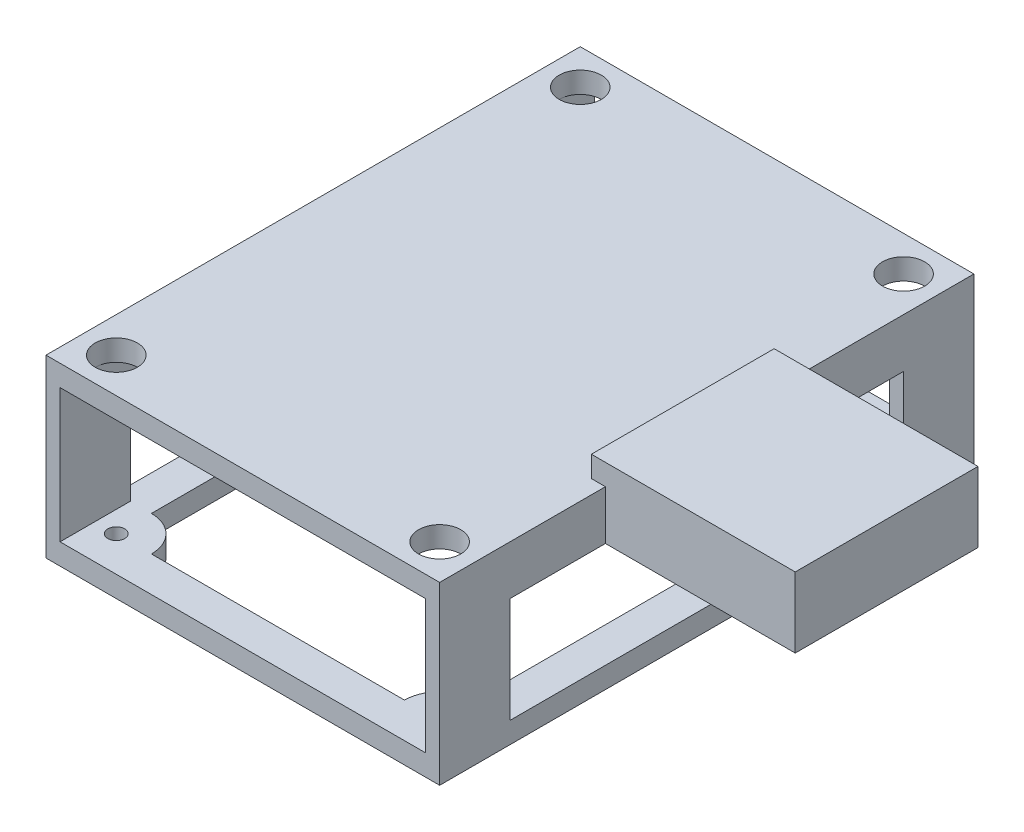
SolidWorks part; units mm, degrees
ref_plane "Front Plane" through (0, 0, 0) normal (0, 0, 1) x (1, 0, 0)
ref_plane "Top Plane" through (0, 0, 0) normal (0, 1, 0) x (1, 0, 0)
ref_plane "Right Plane" through (0, 0, 0) normal (1, 0, 0) x (0, 0, -1)
sketch "Sketch1" plane through (0, 0, 0) normal (0, 1, 0) x (1, 0, 0)
  line L0 (51, 71) -> (51, 5) construction
  line L1 (0, 0) -> (56, 0)
  line L2 (0, 0) -> (0, 76)
  line L3 (0, 76) -> (56, 76)
  line L4 (56, 0) -> (56, 76)
  line L5 (5, 5) -> (51, 5) construction
  circle A0 centre (5, 71) radius 1.2
  circle A1 centre (51, 71) radius 1.2
  circle A2 centre (5, 5) radius 1.2
  circle A3 centre (51, 5) radius 1.2
  point P13 (51, 38)
  point P14 (56, 38)
  point P15 (28, 5)
  point P16 (28, 0)
  dimension "D3" = 2.4
  dimension "D6" = 2.4
  dimension "D7" = 2.4
  dimension "D8" = 2.4
  dimension "D1" = 56
  dimension "D2" = 76
  dimension "D4" = 46
  dimension "D5" = 66
extrude "Boss-Extrude1" add sketch "Sketch1" along normal blind 25
sketch "Sketch2" plane through (0, 0, -76) normal (0, 0, -1) x (-1, 0, 0)
  line L0 (-56, 25) -> (0, 25) construction
  line L1 (-54, 22) -> (-2, 22)
  line L2 (-54, 22) -> (-54, 3)
  line L3 (-54, 3) -> (-2, 3)
  line L4 (-2, 22) -> (-2, 3)
  line L6 (-56, 0) -> (0, 0) construction
  line L7 (-56, 25) -> (-56, 0) construction
  line L8 (0, 25) -> (0, 0) construction
  dimension "D1" = 3
  dimension "D2" = 3
  dimension "D3" = 2
  dimension "D4" = 2
extrude "Cut-Extrude1" cut sketch "Sketch2" against normal through all
sketch "Sketch3" plane through (0, 0, 0) normal (0, -1, 0) x (1, 0, 0)
  line L1 (10, -5) -> (46, -5)
  line L2 (5, -10) -> (5, -66)
  line L3 (10, -71) -> (46, -71)
  line L4 (51, -10) -> (51, -66)
  arc A0 (5, -10) -> (10, -5) centre (5, -5) ccw
  arc A1 (46, -5) -> (51, -10) centre (51, -5) ccw
  arc A2 (51, -66) -> (46, -71) centre (51, -71) ccw
  arc A3 (10, -71) -> (5, -66) centre (5, -71) ccw
extrude "Cut-Extrude2" cut sketch "Sketch3" against normal up to next
sketch "Sketch4" plane through (54, 0, 0) normal (-1, 0, 0) x (0, 0, 1)
  line L0 (0, 3) -> (-76, 3) construction
  line L1 (-66, 3) -> (-10, 3)
  line L2 (-66, 3) -> (-66, 18)
  line L3 (-66, 18) -> (-10, 18)
  line L4 (-10, 3) -> (-10, 18)
  line L5 (-10, 3) -> (-66, 3) construction
  line L6 (-76, 22) -> (-76, 3) construction
  line L7 (0, 22) -> (0, 3) construction
  dimension "D1" = 10
  dimension "D2" = 10
  dimension "D3" = 15
extrude "Cut-Extrude3" cut sketch "Sketch4" against normal through all both and the other way through all
sketch "Sketch7" plane through (0, 25, 0) normal (0, 1, 0) x (1, 0, 0)
  line L0 (28, 76) -> (28, 0) construction
  line L1 (56, 76) -> (0, 76) construction
  line L2 (0, 0) -> (56, 0) construction
  circle A0 centre (5, 71) radius 3
  circle A1 centre (5, 5) radius 3
  circle A2 centre (51, 5) radius 3
  circle A3 centre (51, 71) radius 3
  dimension "D2" = 6
extrude "Cut-Extrude4" cut sketch "Sketch7" against normal up to next and the other way through all
sketch "Sketch8" plane through (56, 0, 0) normal (1, 0, 0) x (0, 0, -1)
  line L0 (10, 18) -> (66, 18) construction
  line L1 (23.5828, 18) -> (49.5828, 18)
  line L2 (23.5828, 18) -> (23.5828, 28)
  line L3 (23.5828, 28) -> (49.5828, 28)
  line L4 (49.5828, 18) -> (49.5828, 28)
  dimension "D1" = 26
  dimension "D2" = 10
sketch "Sketch9" plane through (0, 18, 0) normal (0, -1, 0) x (1, 0, 0)
  line L0 (56, -23.5828) -> (56, -49.5828) construction
  line L1 (56, -23.5828) -> (54, -23.5828)
  line L2 (56, -23.5828) -> (56, -49.5828)
  line L3 (56, -49.5828) -> (54, -49.5828)
  line L4 (54, -23.5828) -> (54, -49.5828)
  line L5 (54, -5) -> (54, -71) construction
extrude "Cut-Extrude7" cut sketch "Sketch9" against normal up to next
sketch "Sketch12" plane through (54, 0, 0) normal (1, 0, 0) x (0, 0, -1)
  line L1 (23.5828, 28) -> (49.5828, 28)
  line L2 (23.5828, 28) -> (23.5828, 18)
  line L3 (23.5828, 18) -> (49.5828, 18)
  line L4 (49.5828, 28) -> (49.5828, 18)
extrude "Boss-Extrude3" add sketch "Sketch12" along normal blind 29
sketch "Sketch13" plane through (0, 18, 0) normal (0, -1, 0) x (1, 0, 0)
  line L0 (54, -23.5828) -> (54, -49.5828) construction
  line L1 (54, -25.5828) -> (81, -25.5828)
  line L2 (54, -25.5828) -> (54, -47.5828)
  line L3 (54, -47.5828) -> (81, -47.5828)
  line L4 (81, -25.5828) -> (81, -47.5828)
  line L5 (83, -23.5828) -> (56, -23.5828) construction
  line L6 (83, -23.5828) -> (83, -49.5828) construction
  line L7 (83, -49.5828) -> (56, -49.5828) construction
  dimension "D1" = 2
  dimension "D2" = 2
  dimension "D3" = 2
extrude "Cut-Extrude8" cut sketch "Sketch13" against normal blind 8.5
sketch "Sketch14" plane through (0, 26.5, 0) normal (0, -1, 0) x (1, 0, 0)
  line L0 (56, -23.5828) -> (56, -49.5828) construction
  line L1 (54, -25.5828) -> (56, -25.5828)
  line L2 (54, -25.5828) -> (54, -47.5828)
  line L3 (54, -47.5828) -> (56, -47.5828)
  line L4 (56, -25.5828) -> (56, -47.5828)
  line L5 (54, -47.5828) -> (81, -47.5828) construction
extrude "Boss-Extrude4" add sketch "Sketch14" along normal blind 4.5
equation "\"D6@Sketch1\"=\"D3@Sketch1\""
equation "\"D7@Sketch1\"=\"D3@Sketch1\""
equation "\"D8@Sketch1\"=\"D3@Sketch1\""
equation "\"D2@Sketch7\"=\"D1@Sketch7\""
